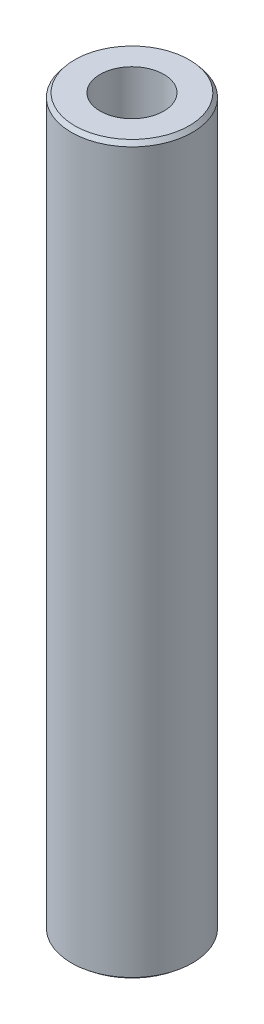
SolidWorks part; units mm, degrees
ref_plane "Front Plane" through (0, 0, 0) normal (0, 0, 1) x (1, 0, 0)
ref_plane "Top Plane" through (0, 0, 0) normal (0, 1, 0) x (1, 0, 0)
ref_plane "Right Plane" through (0, 0, 0) normal (1, 0, 0) x (0, 0, -1)
sketch "Sketch1" plane through (0, 0, 0) normal (0, 1, 0) x (1, 0, 0)
  circle A0 centre (0, 0) radius 50
  dimension "SHAFT_OD" = 100
extrude "Boss-Extrude1" add sketch "Sketch1" along normal blind 600
sketch "Sketch2" plane through (0, 0, 0) normal (0, 1, 0) x (1, 0, 0)
  circle A0 centre (0, 0) radius 26.3071
  dimension "BORE_D" = 52.6143
extrude "Cut-Extrude1" cut sketch "Sketch2" along normal through all
chamfer "Chamfer1" distance 3.3781 angle 39.191 2 edges at (0, 600, 50) (0, 0, 50) first distance on face at (0, 600, 50) first distance on face at (0, 0, 26.3071)
